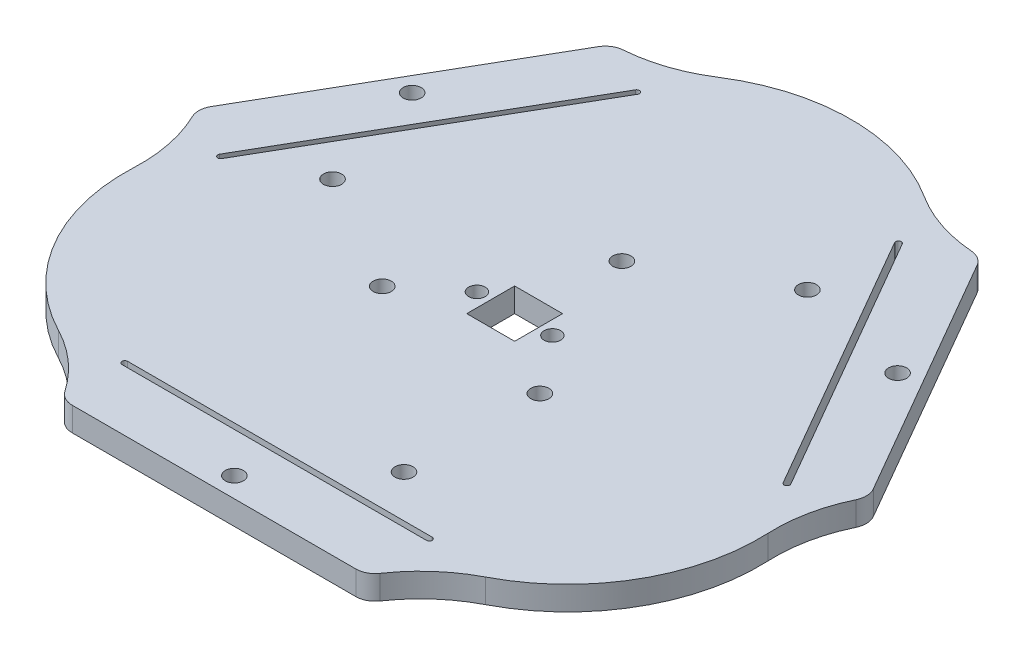
SolidWorks part; units mm, degrees
other "Markup1"
sketch "Sketch7" plane through (-40.4105, 3.175, -42.7327) normal (0, 1, 0) x (1, 0, 0)
material "ABS"
ref_plane "Front Plane" through (0, 0, 0) normal (0, 0, 1) x (1, 0, 0)
ref_plane "Top Plane" through (0, 0, 0) normal (0, 1, 0) x (1, 0, 0)
ref_plane "Right Plane" through (0, 0, 0) normal (1, 0, 0) x (0, 0, -1)
sketch "Sketch4" plane through (0, 0, 0) normal (0, 1, 0) x (1, 0, 0)
  line L6 (-20, 34.8485) -> (20, 34.8485) construction
  line L13 (-20, 34.8485) -> (-40.1796, -0.1038)
  line L14 (0, -34.7447) -> (20.1797, -34.7447)
  line L15 (30.0898, 17.3723) -> (20, 34.8485)
  line L16 (-40.1796, -0.1038) -> (-20.1797, -34.7447) construction
  line L17 (40.1796, -0.1038) -> (20.1797, -34.7447) construction
  line L18 (0, 0) -> (0, 34.8485) construction
  line L19 (0, 0) -> (-30.1796, -17.4242) construction
  line L20 (0, 0) -> (30.1796, -17.4242) construction
  line L21 (-20.1797, -34.7447) -> (0, -34.7447)
  line L22 (40.1796, -0.1038) -> (30.0898, 17.3723)
  line L23 (5, 0) -> (-5, 0) construction
  circle A0 centre (0, 0) radius 34.7447 construction
  arc A2 (20, 34.8485) -> (-20, 34.8485) centre (0, 19.1908) ccw
  arc A5 (20.1797, -34.7447) -> (40.1796, -0.1038) centre (16.6197, -9.5954) ccw
  arc A6 (-40.1796, -0.1038) -> (-20.1797, -34.7447) centre (-16.6197, -9.5954) ccw
  circle A8 centre (-5, 0) radius 1.1
  circle A9 centre (5, 0) radius 1.1
  point P20 (0, 0)
  dimension "D1" = 39.9999
  dimension "D3" = 39.9999
  dimension "D7" = 25.4
  dimension "D8" = 25.4
  dimension "D9" = 25.4
  dimension "D10" = 2.2
  dimension "D2" = 60
  dimension "D4" = 60
  dimension "D5" = 39.9999
  dimension "D6" = 40.3593
  dimension "D11" = 10
extrude "Boss-Extrude4" add sketch "Sketch4" along normal blind 3.175
sketch "Sketch1" plane through (0, 3.175, 0) normal (0, 1, 0) x (1, 0, 0)
  line L6 (10.836, -7.4978) -> (10.836, -25.4978) construction
  line L13 (-28.575, -16.4978) -> (28.575, -16.4978) construction
  line L14 (28.575, -16.4978) -> (0, 32.9956) construction
  line L15 (0, 32.9956) -> (-28.575, -16.4978) construction
  line L16 (16.6637, 22.1331) -> (1.0753, 13.1332) construction
  line L17 (-27.4997, 3.3646) -> (-11.9113, -5.6354) construction
  line L18 (28.575, -16.4978) -> (10.836, -16.4978) construction
  line L19 (-28.575, -16.4978) -> (-19.7055, -1.1354) construction
  line L20 (0, 32.9956) -> (8.8695, 17.6331) construction
  line L22 (40.1796, -0.1038) -> (20, 34.8485) construction
  circle A8 centre (0, 0) radius 16.4978 construction
  circle A9 centre (10.836, -25.4978) radius 1.2
  circle A10 centre (10.836, -7.4978) radius 1.2
  circle A11 centre (-11.9113, -5.6354) radius 1.2
  circle A12 centre (-27.4997, 3.3646) radius 1.2
  circle A13 centre (1.0753, 13.1332) radius 1.2
  circle A14 centre (16.6637, 22.1331) radius 1.2
  point P31 (10.836, -16.4978)
  point P32 (8.8695, 17.6331)
  point P35 (-19.7055, -1.1354)
  dimension "D6" = 2.4
  dimension "D4" = 57.15
  dimension "D5" = 17.739
  dimension "D7" = 18
extrude "Cut-Extrude7" cut sketch "Sketch1" against normal through all
sketch "Sketch5" plane through (0, 3.175, 0) normal (0, 1, 0) x (1, 0, 0)
  line L1 (0, -24.9995) -> (21.6502, -12.4997) construction
  line L2 (21.6502, -12.4997) -> (21.6502, 12.4997) construction
  line L3 (21.6502, 12.4997) -> (0, 24.9995) construction
  line L4 (0, 24.9995) -> (-21.6502, 12.4997) construction
  line L5 (-21.6502, 12.4997) -> (-21.6502, -12.4997) construction
  line L6 (-21.6502, -12.4997) -> (0, -24.9995) construction
  circle A0 centre (0, 0) radius 21.6502 construction
  circle A5 centre (-21.6502, 12.4997) radius 1.2
  circle A8 centre (21.6502, 12.4997) radius 1.2
  circle A9 centre (0, -24.9995) radius 1.2
  dimension "D1" = 43.3003
  dimension "D2" = 2.4
extrude "Cut-Extrude8" [suppressed] cut sketch "Sketch5" against normal through all
sketch "Sketch6" plane through (0, 3.175, 0) normal (0, 1, 0) x (1, 0, 0)
  line L0 (10.836, -7.4978) -> (10.836, -25.4978) construction
  line L1 (10.836, -25.4978) -> (10.836, -34.7447) construction
  line L2 (-20.1797, -34.7447) -> (20.1797, -34.7447) construction
  line L3 (10.836, -34.7447) -> (10.836, -31.4877) construction
  line L4 (10.836, -25.4978) -> (10.836, -7.4978) construction
  line L5 (-20.1797, -31.8624) -> (20.1797, -31.8624)
  line L7 (-20.1797, -31.8624) -> (-20.1797, -31.1129) construction
  line L8 (20.1797, -31.8624) -> (20.1797, -31.1129) construction
  line L9 (0, -31.1129) -> (0, 0) construction
  line L10 (-20.1797, -31.1129) -> (20.1797, -31.1129)
  arc A0 (-20.1797, -31.1129) -> (-20.1797, -31.8624) centre (-20.1797, -31.4877) ccw
  arc A1 (20.1797, -31.1129) -> (20.1797, -31.8624) centre (20.1797, -31.4877) cw
  point P4 (10.836, -16.4978)
  dimension "D2" = 0.3748
  dimension "D1" = 14.9899
  dimension "D3" = 40.3593
extrude "Cut-Extrude9" cut sketch "Sketch6" against normal through all
pattern_circular "CirPattern1" count 3 over 360 about axis through (0, 0, -0.1955) along (0, 1, 0) of "Cut-Extrude9"
sketch "Sketch9" plane through (0, 3.175, 0) normal (0, 1, 0) x (1, 0, 0)
  line L0 (-20, 34.8485) -> (-24.3994, 37.3885)
  line L1 (-24.3994, 37.3885) -> (-44.579, 2.4362)
  line L2 (-44.579, 2.4362) -> (-40.1796, -0.1038)
  line L3 (-20, 34.8485) -> (-40.1796, -0.1038) construction
  line L4 (-20.1797, -34.7447) -> (-20.1797, -39.8247)
  line L5 (-20.1797, -39.8247) -> (20.1797, -39.8247)
  line L6 (20.1797, -34.7447) -> (20.1797, -39.8247)
  line L7 (20, 34.8485) -> (24.3994, 37.3885)
  line L8 (40.1796, -0.1038) -> (20, 34.8485) construction
  line L9 (40.1796, -0.1038) -> (44.579, 2.4362)
  line L10 (24.3994, 37.3885) -> (44.579, 2.4362)
  line L11 (-20, 34.8485) -> (-40.1796, -0.1038)
  line L12 (-20.1797, -34.7447) -> (20.1797, -34.7447)
  line L13 (20, 34.8485) -> (40.1796, -0.1038)
  dimension "D1" = 5.08
extrude "Boss-Extrude5" add sketch "Sketch9" against normal up to surface (3.175 mm away) up to face at (27.4384, 0, -16.037)
sketch "Sketch10" plane through (0, 3.175, 0) normal (0, 1, 0) x (1, 0, 0)
  line L0 (-34.4892, 19.9123) -> (-32.1401, 18.5561) construction
  line L1 (-24.3994, 37.3885) -> (-44.579, 2.4362) construction
  line L2 (-27.763, 16.2244) -> (-27.1138, 15.8497) construction
  line L3 (-17.6731, 33.7005) -> (-37.8528, -1.2517) construction
  line L4 (-37.2037, -1.6264) -> (-17.024, 33.3258) construction
  circle A0 centre (-32.1401, 18.5561) radius 1.2
  point P11 (-27.4384, 16.037)
  dimension "D1" = 2.4
  dimension "D2" = 5.334
extrude "Cut-Extrude10" cut sketch "Sketch10" against normal through all
pattern_circular "CirPattern2" count 3 over 360 about axis through (0.0265, 0, 0.0186) along (0, 1, 0) of "Cut-Extrude10"
sketch "Sketch11" plane through (0, 3.175, 0) normal (0, 1, 0) x (1, 0, 0)
  line L0 (10.836, -7.4978) -> (10.836, -25.4978) construction
  line L1 (10.836, -25.4978) -> (10.836, -16.4978) construction
  line L2 (10.836, -16.4978) -> (-20.914, -16.4978) construction
  line L3 (-12.9765, -16.4978) -> (-12.9765, -10.1478) construction
  line L8 (-12.9765, -10.1478) -> (-28.8515, -10.1478) construction
  line L9 (-28.8515, -10.1478) -> (-28.8515, -26.6578) construction
  line L10 (-28.8515, -26.6578) -> (-12.9765, -26.6578) construction
  line L11 (-12.9765, -26.6578) -> (-12.9765, -16.4978) construction
  line L12 (-12.9765, -10.1478) -> (-20.914, -10.1478) construction
  line L13 (-24.1523, -13.9443) -> (-24.1523, -10.1478) construction
  line L14 (0, -27.8887) -> (24.1523, -13.9443) construction
  line L15 (24.1523, -13.9443) -> (24.1523, 13.9443) construction
  line L16 (24.1523, 13.9443) -> (0, 27.8887) construction
  line L17 (0, 27.8887) -> (-24.1523, 13.9443) construction
  line L18 (-24.1523, 13.9443) -> (-24.1523, -13.9443) construction
  line L19 (-24.1523, -13.9443) -> (0, -27.8887) construction
  line L20 (-24.1523, -13.9443) -> (-12.9765, -20.3967) construction
  line L21 (-12.9765, -26.6578) -> (-12.9765, -20.3967)
  line L22 (-28.8515, -10.1478) -> (-24.1523, -10.1478) construction
  line L23 (16.6637, 22.1331) -> (1.0753, 13.1332) construction
  line L24 (1.0753, 13.1332) -> (8.8695, 17.6331) construction
  line L25 (8.8695, 17.6331) -> (24.7445, -9.8632) construction
  line L26 (29.5746, 2.0909) -> (20.7758, -2.9891) construction
  line L27 (20.7758, -2.9891) -> (15.2765, -6.1641) construction
  line L28 (29.5746, 2.0909) -> (37.5121, -11.6572) construction
  line L29 (24.7445, -9.8632) -> (33.5433, -4.7832) construction
  line L30 (37.5121, -11.6572) -> (23.214, -19.9122) construction
  line L31 (23.214, -19.9122) -> (15.2765, -6.1641) construction
  line L32 (24.1523, -1.0396) -> (24.1523, -13.9443) construction
  line L33 (24.1523, -13.9443) -> (20.8644, -15.8426) construction
  line L34 (29.5746, 2.0909) -> (24.1523, -1.0396)
  line L35 (20.8644, -15.8426) -> (23.214, -19.9122) construction
  line L36 (-27.4997, 3.3646) -> (-11.9113, -5.6354) construction
  line L37 (-11.9113, -5.6354) -> (-19.7055, -1.1354) construction
  line L38 (-19.7055, -1.1354) -> (-3.8305, 26.3609) construction
  line L39 (-8.6606, 38.315) -> (-16.5981, 24.5669) construction
  line L40 (-12.6293, 31.4409) -> (-3.8305, 26.3609) construction
  line L41 (-16.5981, 24.5669) -> (-7.7992, 19.4869) construction
  line L42 (-7.7992, 19.4869) -> (-2.3, 16.3119) construction
  line L43 (-2.3, 16.3119) -> (5.6375, 30.06) construction
  line L44 (5.6375, 30.06) -> (-8.6606, 38.315) construction
  line L45 (-11.1758, 21.4363) -> (0, 27.8887) construction
  line L46 (0, 27.8887) -> (3.2879, 25.9904) construction
  line L47 (3.2879, 25.9904) -> (5.6375, 30.06) construction
  line L48 (-16.5981, 24.5669) -> (-11.1758, 21.4363)
  line L49 (24.1523, -1.0396) -> (24.1523, -11.6572) construction
  line L50 (24.1523, -11.6572) -> (37.5121, -11.6572)
  line L51 (24.1523, -1.0396) -> (24.1523, -11.6572)
  line L53 (-12.9765, -20.3967) -> (-22.1716, -15.0879) construction
  line L54 (-22.1716, -15.0879) -> (-28.8515, -26.6578)
  line L55 (-12.9765, -20.3967) -> (-22.1716, -15.0879)
  line L57 (-11.1758, 21.4363) -> (-1.9807, 26.7451) construction
  line L58 (-1.9807, 26.7451) -> (-8.6606, 38.315)
  line L60 (-11.1758, 21.4363) -> (-1.9807, 26.7451)
  line L61 (-19.7055, -1.1354) -> (-26.3637, -12.6676) construction
  line L62 (-12.9765, -26.6578) -> (-28.8515, -26.6578)
  line L63 (29.5746, 2.0909) -> (37.5121, -11.6572)
  line L64 (-8.6606, 38.315) -> (-16.5981, 24.5669)
  circle A0 centre (0, 0) radius 24.1523 construction
  dimension "D5" = 27.8887
  dimension "D1" = 6.35
  dimension "D2" = 10.16
  dimension "D3" = 15.875
  dimension "D4" = 31.75
extrude "Cut-Extrude11" [suppressed] cut sketch "Sketch11" against normal through all
fillet "Fillet2" [suppressed] radius 2.54
fillet "Fillet3" radius 20.32 6 edges at (-20, 1.5875, -34.8485) (20, 1.5875, -34.8485) (40.1796, 1.5875, 0.1038) (20.1797, 1.5875, 34.7447) (-20.1797, 1.5875, 34.7447) (-40.1796, 1.5875, 0.1038)
fillet "Fillet4" radius 2.54 6 edges at (-20.1797, 1.5875, 39.8247) (20.1797, 1.5875, 39.8247) (44.579, 1.5875, -2.4362) (24.3994, 1.5875, -37.3885) (-24.3994, 1.5875, -37.3885) (-44.579, 1.5875, -2.4362)
sketch "Sketch12" plane through (0, 3.175, 0) normal (0, 1, 0) x (1, 0, 0)
  line L0 (-31.3142, 25.4116) -> (-64.3098, 44.4616)
  line L1 (-25.0952, 36.1833) -> (-43.8832, 3.6414) construction
  line L2 (-72.8729, 42.0732) -> (-34.4892, 19.9123) construction
  line L3 (-70.6598, 33.4631) -> (-37.6642, 14.4131)
  line L4 (-37.6642, 14.4131) -> (-31.3142, 25.4116) construction
  line L5 (-31.3142, 25.4116) -> (-34.4892, 19.9123) construction
  line L6 (-31.3142, 25.4116) -> (-37.6642, 14.4131)
  line L7 (-6.35, -39.8247) -> (-6.35, -77.9247)
  line L8 (-18.788, -39.8247) -> (18.788, -39.8247) construction
  line L9 (6.35, -39.8247) -> (6.35, -77.9247)
  line L10 (37.6642, 14.4131) -> (70.6598, 33.4631)
  line L11 (43.8832, 3.6414) -> (25.0952, 36.1833) construction
  line L12 (31.3142, 25.4116) -> (64.3098, 44.4616)
  line L13 (72.8729, 42.0732) -> (34.4892, 19.9123) construction
  line L14 (31.3142, 25.4116) -> (37.6642, 14.4131)
  line L15 (-6.35, -39.8247) -> (6.35, -39.8247)
  arc A0 (-64.3098, 44.4616) -> (-70.6598, 33.4631) centre (-72.8729, 42.0732) ccw
  arc A1 (70.6598, 33.4631) -> (64.3098, 44.4616) centre (72.8729, 42.0732) ccw
  arc A3 (-6.35, -77.9247) -> (6.35, -77.9247) centre (0, -84.1464) ccw
  point P24 (0, -39.8247)
  dimension "D4" = 6.35
  dimension "D3" = 17.78
  dimension "D5" = 6.35
  dimension "D1" = 6.35
  dimension "D2" = 38.1
  dimension "D6" = 6.35
  dimension "D7" = 6.35
  dimension "D8" = 6.35
extrude "Boss-Extrude6" [suppressed] add sketch "Sketch12" against normal up to surface (3.175 mm away)
sketch "Sketch13" plane through (0, 3.175, 0) normal (0, 1, 0) x (1, 0, 0)
  line L1 (3.175, -3.175) -> (-3.175, -3.175)
  line L2 (3.175, -3.175) -> (3.175, 3.175)
  line L3 (3.175, 3.175) -> (-3.175, 3.175)
  line L4 (-3.175, -3.175) -> (-3.175, 3.175)
  line L5 (3.175, -3.175) -> (-3.175, 3.175) construction
  line L6 (3.175, 3.175) -> (-3.175, -3.175) construction
  point P0 (0, 0)
  dimension "D1" = 6.35
  dimension "D2" = 6.35
extrude "Cut-Extrude12" cut sketch "Sketch13" against normal through all
